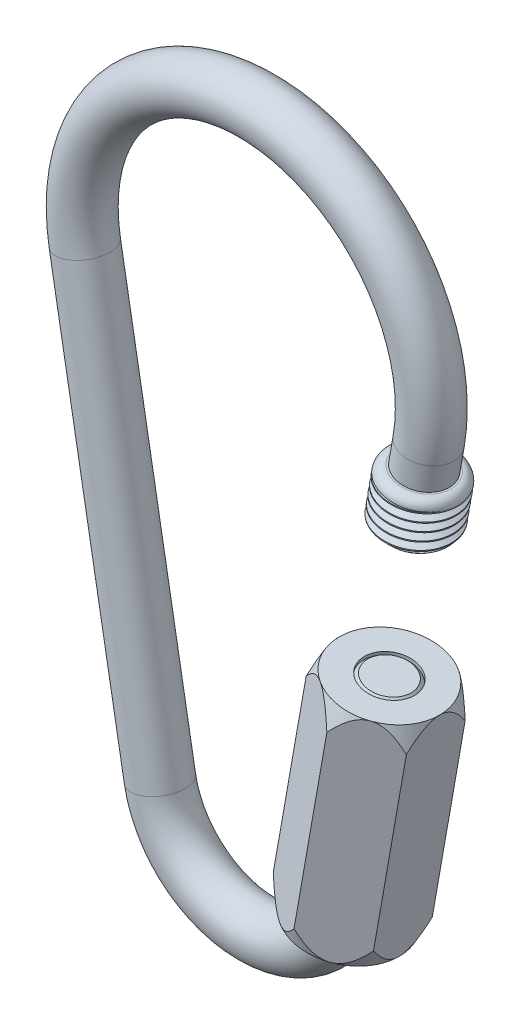
SolidWorks part; units mm, degrees
ref_plane "Front Plane" through (0, 0, 0) normal (0, 0, 1) x (1, 0, 0)
ref_plane "Top Plane" through (0, 0, 0) normal (0, 1, 0) x (1, 0, 0)
ref_plane "Right Plane" through (0, 0, 0) normal (1, 0, 0) x (0, 0, -1)
sketch "Sketch1" plane through (0, 0, 0) normal (0, 0, 1) x (1, 0, 0)
  line L0 (0, -26.25) -> (0, 26.25) construction
  line L1 (-13.75, 0) -> (13.75, 0) construction
  line L2 (-13.5413, 10.1136) -> (-8.371, -19.2252) construction
  line L3 (8.371, -19.2252) -> (13.5413, 10.1136) construction
  line L4 (2.897, -20.0375) -> (9.7907, -21.2524) construction
  line L5 (-10.25, 12.5) -> (-13.75, 12.5) construction
  line L6 (-10.0945, 10.7211) -> (-4.9241, -18.6178) construction
  line L7 (4.9241, -18.6178) -> (10.0945, 10.7211) construction
  line L8 (-1.75, 12.5) -> (1.75, 12.5) construction
  line L9 (5.6738, -4.2803) -> (12.5676, -5.4952) construction
  line L10 (12.5676, -5.4952) -> (9.7907, -21.2524) construction
  line L11 (5.6738, -4.2803) -> (2.897, -20.0375) construction
  line L13 (10.0945, 10.7211) -> (13.5413, 10.1136) construction
  line L14 (9.1207, -4.8877) -> (10.8562, 4.9605) construction
  line L15 (8.371, -19.2252) -> (4.9241, -18.6178) construction
  line L16 (13.9762, 8.26) -> (9.0521, 9.1278) construction
  line L17 (9.0521, 9.1278) -> (8.3942, 5.3944) construction
  line L18 (8.3942, 5.3944) -> (13.3183, 4.5266) construction
  line L19 (13.3183, 4.5266) -> (13.9762, 8.26) construction
  line L20 (13.3917, 4.5533) -> (13.2832, 3.9378) construction
  line L21 (13.2832, 3.9378) -> (12.8044, 4.3395) construction
  line L22 (12.8044, 4.3395) -> (13.3917, 4.5533) construction
  line L23 (12.8044, 4.3395) -> (12.8711, 4.3278) construction
  line L24 (12.8643, 4.2893) -> (12.8778, 4.3663) construction
  line L25 (13.3375, 4.2456) -> (13.2708, 4.2573) construction
  line L26 (13.2234, 3.988) -> (13.3183, 4.5266) construction
  line L27 (13.3042, 4.2515) -> (13.355, 4.54) construction
  line L28 (13.3042, 4.2515) -> (13.2533, 3.9629) construction
  circle A0 centre (0, 12.5) radius 13.75 construction
  circle A1 centre (0, 12.5) radius 10.25 construction
  circle A2 centre (0, -17.75) radius 8.5 construction
  circle A3 centre (0, -17.75) radius 5 construction
  point P4 (0, 0)
  point P7 (0, 0)
  point P9 (13.75, 12.5)
  point P26 (0, 22.75)
  point P27 (0, -22.75)
  point P31 (0, 12.5)
  point P37 (6.3438, -20.6449)
  point P47 (11.8179, 10.4174)
  point P59 (0, 26.25)
  point P62 (-13.75, 0)
  point P63 (10.8562, 4.9605)
  dimension "Wide-End Inside Width" = 20.5
  dimension "Narrow-End Inside Width" = 10
  dimension "Inside Length" = 45.5
  dimension "Thickness" = 3.5
  dimension "Nut Length" = 16
  dimension "Nut Flats" = 7
  dimension "Opening Width" = 10
  dimension "Thread Diameter" = 5
  dimension "Pitch" = 0.625
  dimension "D2" = 0.0781
  dimension "D3" = 1.75
  dimension "D4" = 1.75
  dimension "D5" = 3.7909
sketch "Sketch2" plane through (0, 0, 0) normal (1, 0, 0) x (0, 0, -1)
  line L1 (0, -26.25) -> (0, 26.25) construction
  circle A0 centre (0, 24.5) radius 1.75
sketch "Sketch3" plane through (0, 0, 0) normal (0, 0, 1) x (1, 0, 0)
  line L0 (-13.5413, 10.1136) -> (-8.371, -19.2252) construction
  line L1 (8.371, -19.2252) -> (13.5413, 10.1136) construction
  line L2 (-13.5413, 10.1136) -> (-8.371, -19.2252)
  line L3 (8.371, -19.2252) -> (10.8441, -5.1915)
  line L6 (5.6738, -4.2803) -> (12.5676, -5.4952) construction
  line L7 (8.3942, 5.3944) -> (13.3183, 4.5266) construction
  line L8 (12.5797, 4.6568) -> (13.5413, 10.1136)
  circle A0 centre (0, -17.75) radius 8.5 construction
  circle A1 centre (0, 12.5) radius 13.75 construction
  arc A2 (-8.371, -19.2252) -> (8.371, -19.2252) centre (0, -17.75) ccw
  arc A3 (13.5413, 10.1136) -> (-13.5413, 10.1136) centre (0, 12.5) ccw
sweep "Sweep1" add profiles "Sketch2" path "Sketch3"
sketch "Sketch4" plane through (0, 0, 0) normal (0, 0, 1) x (1, 0, 0)
  line L0 (13.9762, 8.26) -> (9.0521, 9.1278) construction
  line L1 (13.3183, 4.5266) -> (13.9762, 8.26) construction
  line L2 (8.3942, 5.3944) -> (13.3183, 4.5266) construction
  line L4 (13.3607, 8.3685) -> (11.5142, 8.6939)
  line L5 (13.3183, 4.5266) -> (13.8678, 7.6445)
  line L6 (10.8562, 4.9605) -> (13.3183, 4.5266)
  line L8 (10.8562, 4.9605) -> (11.5142, 8.6939)
  arc A0 (13.3607, 8.3685) -> (13.8678, 7.6445) centre (13.2522, 7.753) cw
  point P0 (10.8562, 4.9605)
  dimension "D1" = 0.625
revolve "Revolve1" add sketch "Sketch4" angle 360 about L8
sketch "Sketch5" plane through (-0.5607, -3.1816, 0) normal (0.1736, 0.9848, 0) x (0.9848, -0.1736, 0)
  line L0 (6.3306, 0) -> (13.3306, 0) construction
  line L1 (6.3306, 0) -> (13.3306, 0) construction
  line L3 (6.3306, -2.0207) -> (9.8306, -4.0415)
  line L4 (9.8306, -4.0415) -> (13.3306, -2.0207)
  line L5 (13.3306, -2.0207) -> (13.3306, 2.0207)
  line L6 (13.3306, 2.0207) -> (9.8306, 4.0415)
  line L7 (9.8306, 4.0415) -> (6.3306, 2.0207)
  line L8 (6.3306, 2.0207) -> (6.3306, -2.0207)
  circle A0 centre (9.8306, 0) radius 3.5 construction
  circle A1 centre (9.8306, 0) radius 1.75 construction
  circle A2 centre (9.8306, 0) radius 1.75
extrude "Boss-Extrude1" add sketch "Sketch5" against normal up to vertex (16 mm away) separate body up to point (9.7907, -21.2524, 0)
sketch "Sketch6" plane through (-0.5607, -3.1816, 0) normal (0.1736, 0.9848, 0) x (0.9848, -0.1736, 0)
  circle A0 centre (9.8306, 0) radius 3.5 construction
  circle A1 centre (9.8306, 0) radius 3.5
extrude "Cut-Extrude1" cut sketch "Sketch6" against normal through all draft 20 flip side to cut
sketch "Sketch7" plane through (-3.3375, -18.9388, 0) normal (-0.1736, -0.9848, 0) x (0.9848, -0.1736, 0)
  circle A1 centre (9.8306, 0) radius 3.5
  circle A2 centre (9.8306, 0) radius 3.5
  dimension "D1" = 0
extrude "Cut-Extrude2" cut sketch "Sketch7" against normal through all draft 20 flip side to cut
chamfer "Chamfer1" distance 0.4688 angle 45 1 edges at (13.3183, 4.5266, 0)
chamfer "Chamfer2" distance 0.2344 angle 45 1 edges at (9.1207, -4.8877, -1.75)
sketch "Sketch8" plane through (0, 0, 0) normal (0, 0, 1) x (1, 0, 0)
  line L0 (13.355, 4.54) -> (13.2533, 3.9629)
  line L1 (13.2533, 3.9629) -> (12.8643, 4.2893)
  line L2 (12.8643, 4.2893) -> (12.8778, 4.3663)
  line L3 (12.8778, 4.3663) -> (13.355, 4.54)
sketch "Sketch9" plane through (1.1748, 6.6666, 0) normal (-0.1736, -0.9848, 0) x (0.9848, -0.1736, 0)
  circle A1 centre (9.8306, 0) radius 2.0312
  circle A3 centre (9.8306, 0) radius 2.0312
  dimension "D1" = 0
curve "Helix/Spiral1" pitch 0.625 height 4.4159 turns 7.0655
sweep "Cut-Sweep1" cut profiles "Sketch8" path "Helix/Spiral1"
sketch "Sketch10" plane through (0, 0, 0) normal (0, 0, 1) x (1, 0, 0)
  line L0 (11.5142, 8.6939) -> (13.3607, 8.3685)
  line L1 (13.9762, 8.26) -> (9.0521, 9.1278) construction
  line L2 (11.5142, 8.6939) -> (11.4057, 8.0784)
  line L3 (10.8562, 4.9605) -> (11.5142, 8.6939) construction
  line L4 (11.4057, 8.0784) -> (13.8678, 7.6445)
  arc A0 (13.8678, 7.6445) -> (13.3607, 8.3685) centre (13.2522, 7.753) ccw construction
  arc A1 (13.8678, 7.6445) -> (13.3607, 8.3685) centre (13.2522, 7.753) ccw
revolve "Revolve2" add sketch "Sketch10" angle 360 about L8
sketch "Sketch11" plane through (0, 0, 0) normal (0, 0, 1) x (1, 0, 0)
  circle A1 centre (0.523, 14.2415) radius 10.0033
  point P1 (0.523, 14.2415)
equation "\"Nut Flats@Sketch1\"=\"Thickness@Sketch1\"*2"
equation "\"D2@Sketch1\"=\"Pitch@Sketch1\"/8"
equation "\"Pitch@Sketch1\"=\"Thread Diameter@Sketch1\" / 8"
equation "\"D1@Sketch4\"=\"Pitch@Sketch1\""
equation "\"D3@Sketch1\"=\"Thickness@Sketch1\"*.5"
equation "\"D4@Sketch1\"=\"D3@Sketch1\""
equation "\"D4@Helix/Spiral1\"=\"Pitch@Sketch1\""
equation "\"D3@Helix/Spiral1\"=\"D5@Sketch1\"+\"Pitch@Sketch1\""
equation "\"D1@Chamfer1\"=\"Pitch@Sketch1\"*.75"
equation "\"D1@Chamfer2\"=\"D1@Chamfer1\"*.5"
